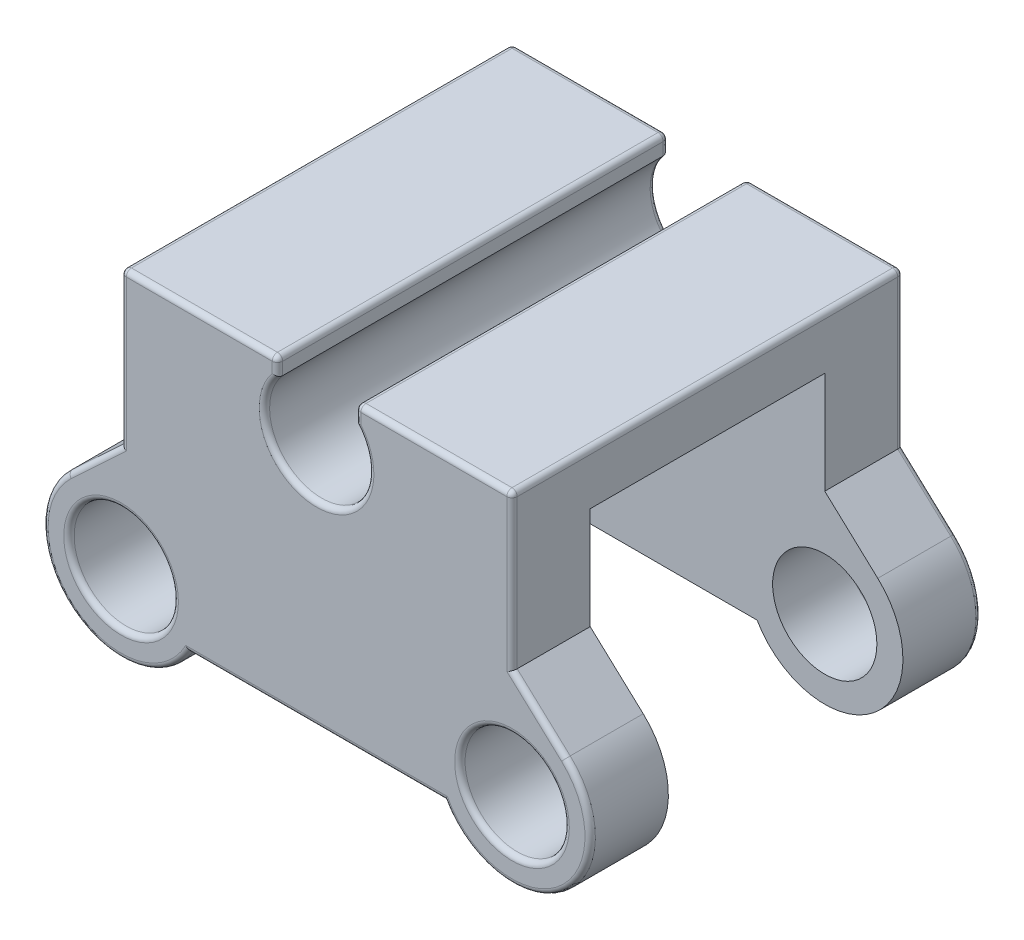
SolidWorks part; units mm, degrees
ref_plane "前视基准面" through (0, 0, 0) normal (0, 0, 1) x (1, 0, 0)
ref_plane "上视基准面" through (0, 0, 0) normal (0, 1, 0) x (1, 0, 0)
ref_plane "右视基准面" through (0, 0, 0) normal (1, 0, 0) x (0, 0, -1)
sketch "草图1" plane through (0, 0, 0) normal (0, 0, 1) x (1, 0, 0)
  line L0 (3, -2) -> (7.5, -2)
  line L1 (-7.5, 0) -> (1.5, 0)
  line L2 (-7.5, 0) -> (-7.5, -2)
  line L3 (-7.5, -2) -> (-3, -2)
  line L4 (7.5, 0) -> (7.5, -2)
  line L7 (1.5, 0) -> (7.5, 0)
  arc A1 (-3, -2) -> (3, -2) centre (0, -2) ccw
extrude "凸台-拉伸1" add sketch "草图1" along normal blind 4.5 and the other way blind 4.5
sketch "草图2" plane through (0, 0, 4.5) normal (0, 0, 1) x (1, 0, 0)
  line L0 (9.5344, -7.7952) -> (7.5, -5.9181)
  line L1 (-7.5, 0) -> (7.5, 0)
  line L2 (-7.5, 0) -> (-7.5, -5.8969)
  line L3 (-4.9019, -11.5) -> (4.9019, -11.5)
  line L4 (7.5, 0) -> (7.5, -5.9181)
  line L5 (-9.5466, -7.8065) -> (-7.5, -5.8969)
  circle A0 centre (-7.5, -10) radius 2
  circle A1 centre (7.5, -10) radius 2
  arc A2 (-9.5466, -7.8065) -> (-4.9019, -11.5) centre (-7.5, -10) ccw
  arc A3 (4.9019, -11.5) -> (9.5344, -7.7952) centre (7.5, -10) ccw
extrude "凸台-拉伸2" add sketch "草图2" along normal blind 3
extrude "凸台-拉伸3" add sketch "草图2<2>" against normal blind 3 from offset 9 offset against normal yes
sketch "草图2<2>" plane through (0, 0, 4.5) normal (0, 0, 1) x (1, 0, 0) same geometry as "草图2"
sketch "草图3" plane through (0, 0, 7.5) normal (0, 0, 1) x (1, 0, 0)
  line L0 (-1.5, 0) -> (1.5, 0)
  line L2 (-1.5, 0) -> (-1.5, -0.6771)
  line L4 (1.5, 0) -> (1.5, -0.6771)
  line L5 (7.5, 0) -> (-7.5, 0) construction
  arc A0 (-1.5, -0.6771) -> (1.5, -0.6771) centre (0, -2) ccw
extrude "切除-拉伸1" cut sketch "草图3" against normal up to next
fillet "圆角1" radius 0.2 32 edges at (-7.5, 0, 0) (-1.5, 0, 0) (7.5, 0, 0) (1.5, 0, 0) (-7.5, -2.9485, -7.5) (-8.5233, -6.8517, -7.5) (-9.3672, -12.3481, -7.5) (0, -11.5, -7.5) (9.3737, -12.3429, -7.5) (8.5172, -6.8566, -7.5) (7.5, -2.959, -7.5) (4.5, 0, -7.5) (1.5, -0.3386, -7.5) (0, -4, -7.5) (-1.5, -0.3386, -7.5) (-4.5, 0, -7.5) (-5.5, -10, -7.5) (9.5, -10, -7.5) (9.5, -10, 7.5) (-5.5, -10, 7.5) (0, -4, 7.5) (1.5, -0.3386, 7.5) (4.5, 0, 7.5) (7.5, -2.959, 7.5) (8.5172, -6.8566, 7.5) (9.3737, -12.3429, 7.5) (0, -11.5, 7.5) (-9.3672, -12.3481, 7.5) (-8.5233, -6.8517, 7.5) (-7.5, -2.9485, 7.5) (-4.5, 0, 7.5) (-1.5, -0.3386, 7.5)
